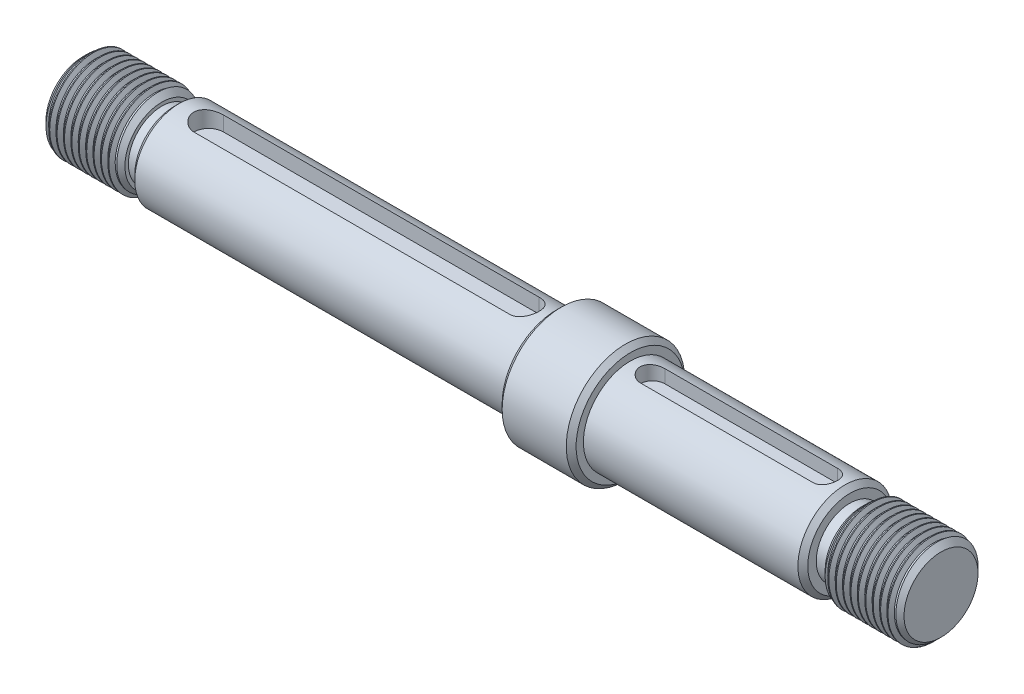
SolidWorks part; units mm, degrees
material "1.0503 (C45)"
ref_plane "前视基准面" through (0, 0, 0) normal (0, 0, 1) x (1, 0, 0)
ref_plane "上视基准面" through (0, 0, 0) normal (0, 1, 0) x (1, 0, 0)
ref_plane "右视基准面" through (0, 0, 0) normal (1, 0, 0) x (0, 0, -1)
sketch "轴轴向刨面" plane through (0, 0, 0) normal (0, 0, 1) x (1, 0, 0)
  line L0 (0, 0) -> (0, 9)
  line L3 (18.5, 9) -> (96, 9)
  line L4 (96, 9) -> (96, 12)
  line L5 (96, 12) -> (111, 12)
  line L6 (111, 12) -> (111, 9.525)
  line L7 (111, 9.525) -> (155.5, 9.525)
  line L8 (174, 9) -> (174, 0)
  line L9 (174, 0) -> (0, 0)
  line L10 (158, 9) -> (174, 9)
  line L12 (18.5, 6.8) -> (16, 6.8)
  line L13 (16, 6.8) -> (16, 9)
  line L14 (0, 9) -> (16, 9)
  line L16 (155.5, 9.525) -> (155.5, 6.8)
  line L17 (155.5, 6.8) -> (158, 6.8)
  line L18 (158, 6.8) -> (158, 9)
  line L19 (18.5, 9) -> (18.5, 6.8)
  line L20 (-35.4351, 0) -> (195.3106, 0) construction
  dimension "D6" = 18
  dimension "D1" = 44.5
  dimension "D2" = 19.05
  dimension "D3" = 77.5
  dimension "D4" = 15
  dimension "D5" = 2.5
  dimension "D8" = 13.6
  dimension "轴肩半径" = 24
  dimension "大端螺纹长度" = 16
revolve "旋转轴" add sketch "轴轴向刨面" angle 360 about L9
ref_plane "9mm键槽面" through (0, 9, 0) normal (0, 1, 0) x (1, 0, 0)
sketch "草图24" plane through (0, 9, 0) normal (0, 1, 0) x (1, 0, 0)
  line L0 (25.5, 0) -> (89.5, 0) construction
  line L3 (25.5, 3) -> (89.5, 3)
  line L4 (25.5, -3) -> (89.5, -3)
  line L5 (18.5, 6.8) -> (18.5, -6.8) construction
  line L6 (96, 12) -> (96, -12) construction
  arc A2 (25.5, 3) -> (25.5, -3) centre (25.5, 0) ccw
  arc A3 (89.5, -3) -> (89.5, 3) centre (89.5, 0) ccw
  point P2 (57.5, 0)
  point P11 (22.5, 0)
  point P12 (92.5, 0)
  dimension "D2" = 6
  dimension "D1" = 4
  dimension "D3" = 3.5
  dimension "D4" = 70
extrude "切除-拉伸11" cut sketch "草图24" against normal blind 3.5
ref_plane "9.52mm键槽面" through (0, 9.525, 0) normal (0, 1, 0) x (1, 0, 0)
sketch "草图25" plane through (0, 9.525, 0) normal (0, 1, 0) x (1, 0, 0)
  line L0 (115.5, 0) -> (150.5, 0) construction
  line L1 (111, 0) -> (155.5, 0) construction
  line L2 (115.5, 2.5) -> (150.5, 2.5)
  line L3 (115.5, -2.5) -> (150.5, -2.5)
  line L5 (155.5, -9.525) -> (155.5, 9.525) construction
  line L6 (111, -9.525) -> (111, 9.525) construction
  arc A0 (115.5, 2.5) -> (115.5, -2.5) centre (115.5, 0) ccw
  arc A1 (150.5, -2.5) -> (150.5, 2.5) centre (150.5, 0) ccw
  point P5 (133, 0)
  point P14 (153, 0)
  point P15 (113, 0)
  dimension "D2" = 2
  dimension "D1" = 5
  dimension "D3" = 2.5
  dimension "D4" = 40
extrude "切除-拉伸12" cut sketch "草图25" against normal blind 3
sketch "草图30" plane through (0, 0, 0) normal (-1, 0, 0) x (0, 0, 1)
  circle A0 centre (0, 0) radius 9 construction
  circle A1 centre (0, 0) radius 9
chamfer "倒角1" distance 1.5 angle 45 4 edges at (174, 0, -9) (158, 0, -9) (16, 0, -9) (0, 0, -9)
chamfer "倒角2" distance 1 angle 45 4 edges at (18.5, 0, -9) (96, 0, -12) (111, 0, -12) (155.5, 0, -9.525)
thread "螺纹线1" pitch 1.5 method cut profile "螺纹线轮廓1" start angle 0, offset 1.5, length 16, pitch 1.5, diameter 18
ref_plane "基准面1" through (0, 0, -9) normal (0, -1, 0) x (0, 0, -1)
sketch "螺纹线轮廓1" plane through (0, 0, -9) normal (0, -1, 0) x (0, 0, -1)
  line L0 (0, 0) -> (0, 1.5) construction
  line L11 (0, 0) -> (0, 1.3125)
  line L12 (0, 1.3125) -> (-0.8119, 0.8437)
  line L13 (-0.8119, 0.8437) -> (-0.8119, 0.4687)
  line L15 (-0.8119, 0.4687) -> (0, 0)
  line L17 (-0.8119, 0.6562) -> (0, 0.6562) construction
  point P2 (0, 0)
  dimension "Pitch" = 1.5
  dimension "Profile_Angle" = 60
  dimension "Profile_Land" = 0.375
  dimension "Profile_Height" = 0.8119
thread "螺纹线2" pitch 1.5 method cut profile "螺纹线轮廓2" start angle 0, offset 1.5, length 16, pitch 1.5, diameter 18
ref_plane "基准面2" through (158, 0, -9) normal (0, -1, 0) x (0, 0, -1)
sketch "螺纹线轮廓2" plane through (158, 0, -9) normal (0, -1, 0) x (0, 0, -1)
  line L0 (0, 0) -> (0, 1.5) construction
  line L11 (0, 0) -> (0, 1.3125)
  line L12 (0, 1.3125) -> (-0.8119, 0.8437)
  line L13 (-0.8119, 0.8437) -> (-0.8119, 0.4687)
  line L15 (-0.8119, 0.4687) -> (0, 0)
  line L17 (-0.8119, 0.6562) -> (0, 0.6562) construction
  point P2 (0, 0)
  dimension "Pitch" = 1.5
  dimension "Profile_Angle" = 60
  dimension "Profile_Land" = 0.375
  dimension "Profile_Height" = 0.8119
